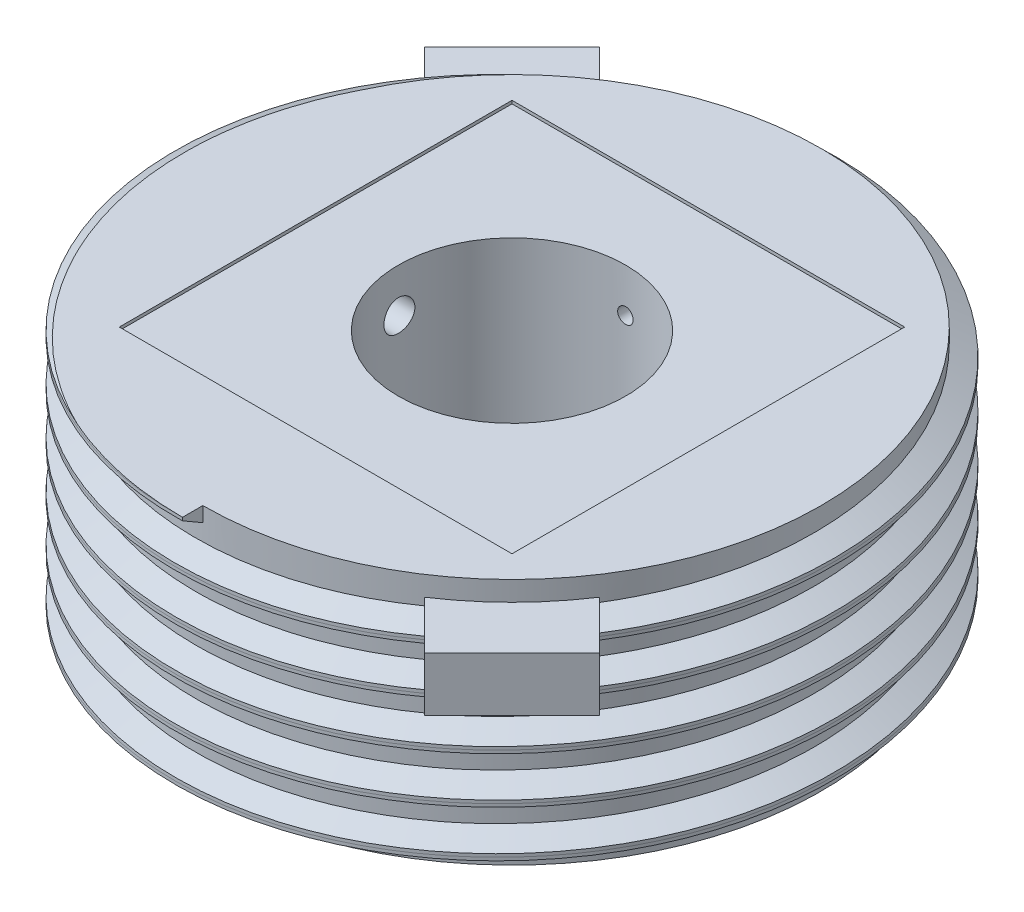
SolidWorks part; units mm, degrees
ref_plane "Front Plane" through (0, 0, 0) normal (0, 0, 1) x (1, 0, 0)
ref_plane "Top Plane" through (0, 0, 0) normal (0, 1, 0) x (1, 0, 0)
ref_plane "Right Plane" through (0, 0, 0) normal (1, 0, 0) x (0, 0, -1)
sketch "innerCircle" plane through (0, 0, 0) normal (0, 1, 0) x (1, 0, 0)
  circle A0 centre (0, 0) radius 7.35
  circle A1 centre (0, 0) radius 20
  dimension "D1" = 14.7
  dimension "D2" = 40
extrude "Circle" add sketch "innerCircle" along normal blind 16
sketch "Sketch5" plane through (0, 16, 0) normal (0, 1, 0) x (1, 0, 0)
  line L1 (12.7, 12.7) -> (-12.7, 12.7)
  line L2 (12.7, 12.7) -> (12.7, -12.7)
  line L3 (12.7, -12.7) -> (-12.7, -12.7)
  line L4 (-12.7, 12.7) -> (-12.7, -12.7)
  line L5 (12.7, 12.7) -> (-12.7, -12.7) construction
  line L6 (12.7, -12.7) -> (-12.7, 12.7) construction
  point P0 (0, 0)
  dimension "D1" = 25.4
  dimension "D2" = 25.4
sketch "Sketch11" plane through (0, 0, 0) normal (0, 0, 1) x (1, 0, 0)
  line L0 (0, 16) -> (0, 0) construction
  point P5 (0, 0)
  point P6 (0, 0)
ref_plane "Plane1" through (0, 16, 0) normal (0, 1, 0) x (1, 0, 0)
sketch "Sketch13" plane through (0, 16, 0) normal (0, 1, 0) x (1, 0, 0)
  circle A0 centre (0, 0) radius 20
curve "Helix/Spiral1" pitch 3 height 16 radius 20 centre (0, 16, 0) axis (0, -1, 0) start towards (0, 0, 1)
sketch "Sketch14" plane through (0, 0, 0) normal (1, 0, 0) x (0, 0, -1)
  line L0 (-19.8126, 16) -> (-21.3126, 16) construction
  line L1 (20, 16) -> (-20, 16) construction
  line L2 (-21.3126, 16) -> (-21.3126, 16.2)
  line L3 (-21.3126, 16.2) -> (-19.8126, 17.066)
  line L4 (-19.8126, 17.066) -> (-19.8126, 14.934)
  line L5 (-19.8126, 14.934) -> (-21.3126, 15.8)
  line L6 (-21.3126, 15.8) -> (-21.3126, 16)
  dimension "D1" = 1.5
  dimension "D2" = 60
  dimension "D3" = 0.2
sweep "Sweep1" add profiles "Sketch14" path "Helix/Spiral1"
sketch "Sketch15" plane through (0, 0, 0) normal (1, 0, 0) x (0, 0, -1)
  line L0 (0, 16) -> (0, 0) construction
  circle A0 centre (0, 12.9718) radius 1
  dimension "D1" = 2
sketch "Sketch16" plane through (0, 0, 0) normal (0, 0, 1) x (1, 0, 0)
  line L0 (0, 11.9718) -> (0, 13.9718) construction
  circle A0 centre (0, 12.9718) radius 0.5
  dimension "D1" = 1
extrude "Cut-Extrude2" cut sketch "Sketch16" against normal through all
extrude "Cut-Extrude3" cut sketch "Sketch15" against normal through all
ref_plane "Plane2" through (0, 0, 0) normal (0.7071, 0, 0.7071) x (0, -1, 0)
sketch "Sketch17" plane through (0, 0, 0) normal (0.7071, 0, 0.7071) x (0, -1, 0)
  line L1 (-11.2218, -4) -> (-14.7218, -4)
  line L2 (-11.2218, -4) -> (-11.2218, 4)
  line L3 (-11.2218, 4) -> (-14.7218, 4)
  line L4 (-14.7218, -4) -> (-14.7218, 4)
  line L5 (-11.2218, -4) -> (-14.7218, 4) construction
  line L6 (-11.2218, 4) -> (-14.7218, -4) construction
  point P0 (-12.9718, 0)
  dimension "D1" = 8
  dimension "D2" = 3.5
extrude "Boss-Extrude1" add sketch "Sketch17" along normal blind 24 and the other way blind 24
sketch "Sketch18" plane through (0, 0, 0) normal (0, 1, 0) x (1, 0, 0)
  circle A0 centre (0, 0) radius 7.35
  dimension "D1" = 14.7
extrude "Cut-Extrude4" cut sketch "Sketch18" along normal through all
sketch "Sketch19" plane through (0, 0, 0) normal (1, 0, 0) x (0, 0, -1)
  line L0 (25, -2) -> (-25, -2) construction
  line L1 (-19.9189, 0) -> (20.6045, 0)
  line L2 (-19.9189, 0) -> (-19.9189, -2)
  line L3 (-19.9189, -2) -> (20.6045, -2)
  line L4 (20.6045, 0) -> (20.6045, -2)
  spline S0 degree 2 poles (-16.6848, 12.3216) (-20, 12.1809) (-20, 12.0422) (-20, 11.8922) (-16.1803, 11.7422) (-12.3607, 11.5922) (-6.1803, 11.4422) (0, 11.2922) (6.1803, 11.1422) (12.3607, 10.9922) (16.1803, 10.8422) (20, 10.6922) (20, 10.5422) (20, 10.3922) (16.1803, 10.2422) (12.3607, 10.0922) (6.1803, 9.9422) (0, 9.7922) (-6.1803, 9.6422) (-12.3607, 9.4922) (-16.1803, 9.3422) (-20, 9.1922) (-20, 9.0422) (-20, 8.8922) (-16.1803, 8.7422) (-12.3607, 8.5922) (-6.1803, 8.4422) (0, 8.2922) (6.1803, 8.1422) (12.3607, 7.9922) (16.1803, 7.8422) (20, 7.6922) (20, 7.5422) (20, 7.3922) (16.1803, 7.2422) (12.3607, 7.0922) (6.1803, 6.9422) (0, 6.7922) (-6.1803, 6.6422) (-12.3607, 6.4922) (-16.1803, 6.3422) (-20, 6.1922) (-20, 6.0422) (-20, 5.8922) (-16.1803, 5.7422) (-12.3607, 5.5922) (-6.1803, 5.4422) (0, 5.2922) (6.1803, 5.1422) (12.3607, 4.9922) (16.1803, 4.8422) (20, 4.6922) (20, 4.5422) (20, 4.3922) (16.1803, 4.2422) (12.3607, 4.0922) (6.1803, 3.9422) (0, 3.7922) (-6.1803, 3.6422) (-12.3607, 3.4922) (-16.1803, 3.3422) (-20, 3.1922) (-20, 3.0422) (-20, 2.8922) (-16.1803, 2.7422) (-12.3607, 2.5922) (-6.1803, 2.4422) (0, 2.2922) (6.1803, 2.1422) (12.3607, 1.9922) (16.1803, 1.8422) (20, 1.6922) (20, 1.5422) (20, 1.3922) (16.1803, 1.2422) (12.3607, 1.0922) (6.1803, 0.9422) (0, 0.7922) (-6.1803, 0.6422) (-12.3607, 0.4922) (-16.1803, 0.3422) (-20, 0.1922) (-20, 0.0422) (-20, 0.0213) (-19.9189, 0) knots 0.15119 0.15119 0.15119 0.166667 0.166667 0.183333 0.183333 0.2 0.2 0.216667 0.216667 0.233333 0.233333 0.25 0.25 0.266667 0.266667 0.283333 0.283333 0.3 0.3 0.316667 0.316667 0.333333 0.333333 0.35 0.35 0.366667 0.366667 0.383333 0.383333 0.4 0.4 0.416667 0.416667 0.433333 0.433333 0.45 0.45 0.466667 0.466667 0.483333 0.483333 0.5 0.5 0.516667 0.516667 0.533333 0.533333 0.55 0.55 0.566667 0.566667 0.583333 0.583333 0.6 0.6 0.616667 0.616667 0.633333 0.633333 0.65 0.65 0.666667 0.666667 0.683333 0.683333 0.7 0.7 0.716667 0.716667 0.733333 0.733333 0.75 0.75 0.766667 0.766667 0.783333 0.783333 0.8 0.8 0.816667 0.816667 0.833333 0.833333 0.835748 0.835748 0.835748 weights 0.993509 0.954551 1 0.951057 1 0.951057 1 0.951057 1 0.951057 1 0.951057 1 0.951057 1 0.951057 1 0.951057 1 0.951057 1 0.951057 1 0.951057 1 0.951057 1 0.951057 1 0.951057 1 0.951057 1 0.951057 1 0.951057 1 0.951057 1 0.951057 1 0.951057 1 0.951057 1 0.951057 1 0.951057 1 0.951057 1 0.951057 1 0.951057 1 0.951057 1 0.951057 1 0.951057 1 0.951057 1 0.951057 1 0.951057 1 0.951057 1 0.951057 1 0.951057 1 0.951057 1 0.951057 1 0.951057 1 0.951057 1 0.951057 1 0.99291 0.987874 construction
  dimension "D1" = 40.5234
  dimension "D2" = 2
extrude "Cut-Extrude5" cut sketch "Sketch19" against normal through all both and the other way through all
sketch "Sketch20" plane through (0, 0, 0) normal (1, 0, 0) x (0, 0, -1)
  line L1 (20, 16) -> (-21.3126, 16)
  line L2 (20, 16) -> (20, 18.2403)
  line L3 (20, 18.2403) -> (-21.3126, 18.2403)
  line L4 (-21.3126, 16) -> (-21.3126, 18.2403)
  dimension "D1" = 41.3126
  dimension "D2" = 2.2403
extrude "Cut-Extrude6" cut sketch "Sketch20" against normal through all both and the other way through all
sketch "Sketch21" plane through (0, 0, 0) normal (0, -1, 0) x (1, 0, 0)
  circle A0 centre (0, 0) radius 14
  circle A1 centre (0, 0) radius 12.3
  dimension "D1" = 28
  dimension "D2" = 1.7
extrude "Cut-Extrude7" cut sketch "Sketch21" against normal blind 0.7
sketch "Sketch22" plane through (0, 16, 0) normal (0, 1, 0) x (1, 0, 0)
  line L1 (-12.7, -12.7) -> (12.7, -12.7)
  line L2 (-12.7, -12.7) -> (-12.7, 12.7)
  line L3 (-12.7, 12.7) -> (12.7, 12.7)
  line L4 (12.7, -12.7) -> (12.7, 12.7)
  line L5 (-12.7, -12.7) -> (12.7, 12.7) construction
  line L6 (-12.7, 12.7) -> (12.7, -12.7) construction
  point P0 (0, 0)
extrude "Cut-Extrude8" cut sketch "Sketch22" against normal blind 0.2
equation "\"1inch\"=30"
